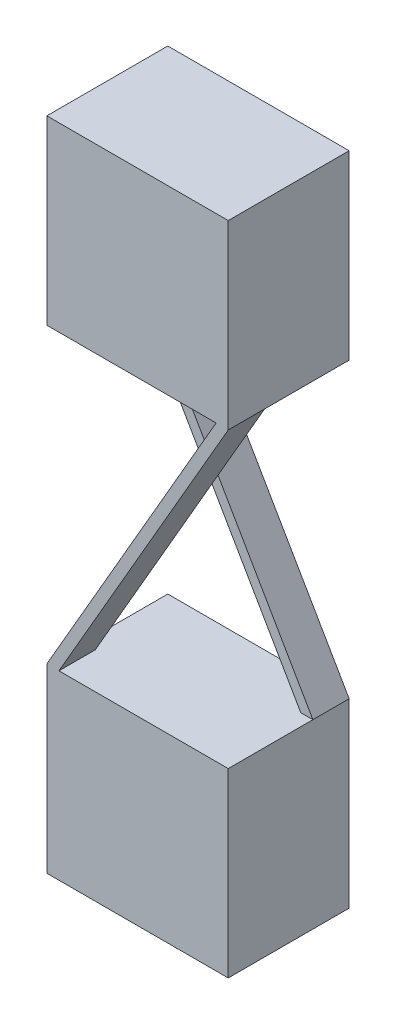
SolidWorks part; units mm, degrees
material "PET"
ref_plane "Front Plane" through (0, 0, 0) normal (0, 0, 1) x (1, 0, 0)
ref_plane "Top Plane" through (0, 0, 0) normal (0, 1, 0) x (1, 0, 0)
ref_plane "Right Plane" through (0, 0, 0) normal (1, 0, 0) x (0, 0, -1)
sketch "Sketch1" plane through (0, 0, 0) normal (0, 0, 1) x (1, 0, 0)
  line L0 (0, 0) -> (57.9688, 0) construction
  line L1 (7.5, 12.1244) -> (-7.5, 12.1244)
  line L2 (7.5, -27.1244) -> (-7.5, -27.1244)
  line L3 (7.5, -27.1244) -> (7.5, -12.1244)
  line L4 (7.5, -12.1244) -> (-7.5, -12.1244)
  line L5 (-7.5, -27.1244) -> (-7.5, -12.1244)
  line L6 (7.5, -27.1244) -> (-7.5, -12.1244) construction
  line L7 (7.5, -12.1244) -> (-7.5, -27.1244) construction
  line L8 (-7.5, 27.1244) -> (-7.5, 12.1244)
  line L9 (0, 0) -> (0, 41.5625) construction
  line L10 (7.5, 27.1244) -> (-7.5, 27.1244)
  line L11 (7.5, 27.1244) -> (7.5, 12.1244)
  line L12 (-7.5, 12.1244) -> (6.5, -12.1244)
  line L13 (6.5, -12.1244) -> (7.5, -12.1244)
  line L14 (7.5, -12.1244) -> (-6.5, 12.1244)
  line L15 (-6.5, 12.1244) -> (-7.5, 12.1244)
  line L16 (7.5, 12.1244) -> (-6.5, -12.1244)
  line L17 (-7.5, -12.1244) -> (6.5, 12.1244)
  point P1 (0, -19.6244)
  dimension "D1" = 15
  dimension "D2" = 60
  dimension "D3" = 1
extrude "Boss-Extrude1" add sketch "Sketch1" along normal mid plane 10 contours L11 L10 L8 L1 | L5 L2 L3 L4 region at (0, 19.6244, 0) region at (0, -19.6244, 0)
extrude "Boss-Extrude2" add sketch "Sketch1<3>" against normal blind 3 from surface contours L17 L4 L16 L12 | L17 L14 L16 L1 | L17 L12 L16 L14 region at (3.6296, 6.276, 0) region at (0, 0, 0) region at (-3.6296, -6.276, 0) starting at face at (0, -19.6244, 5)
sketch "Sketch1<3>" plane through (0, 0, 0) normal (0, 0, 1) x (1, 0, 0) same geometry as "Sketch1"
extrude "Boss-Extrude3" add sketch "Sketch1<4>" along normal blind 3 from surface contours L12 L17 L14 L1 | L14 L16 L12 L4 | L17 L12 L16 L14 region at (0, 0, 0) region at (3.6296, -6.276, 0) region at (-3.6296, 6.276, 0) starting at face at (0, -19.6244, -5)
sketch "Sketch1<4>" plane through (0, 0, 0) normal (0, 0, 1) x (1, 0, 0) same geometry as "Sketch1"
ref_plane "Plane1" through (0, 19.6244, 0) normal (0, -1, 0) x (-1, 0, 0)
equation "\"a\"= 3"
equation "\"D1@Boss-Extrude2\"=\"a\""
equation "\"D1@Boss-Extrude3\"= \"a\""
equation "\"side\"= 15"
equation "\"angle\"= 60deg"
equation "\"D2@Sketch1\"=\"angle\""
equation "\"D1@Sketch1\"=\"side\""
equation "\"spacing\"= \"side\" / tan ( \"angle\" ) + \"side\"'for linear pattern"
